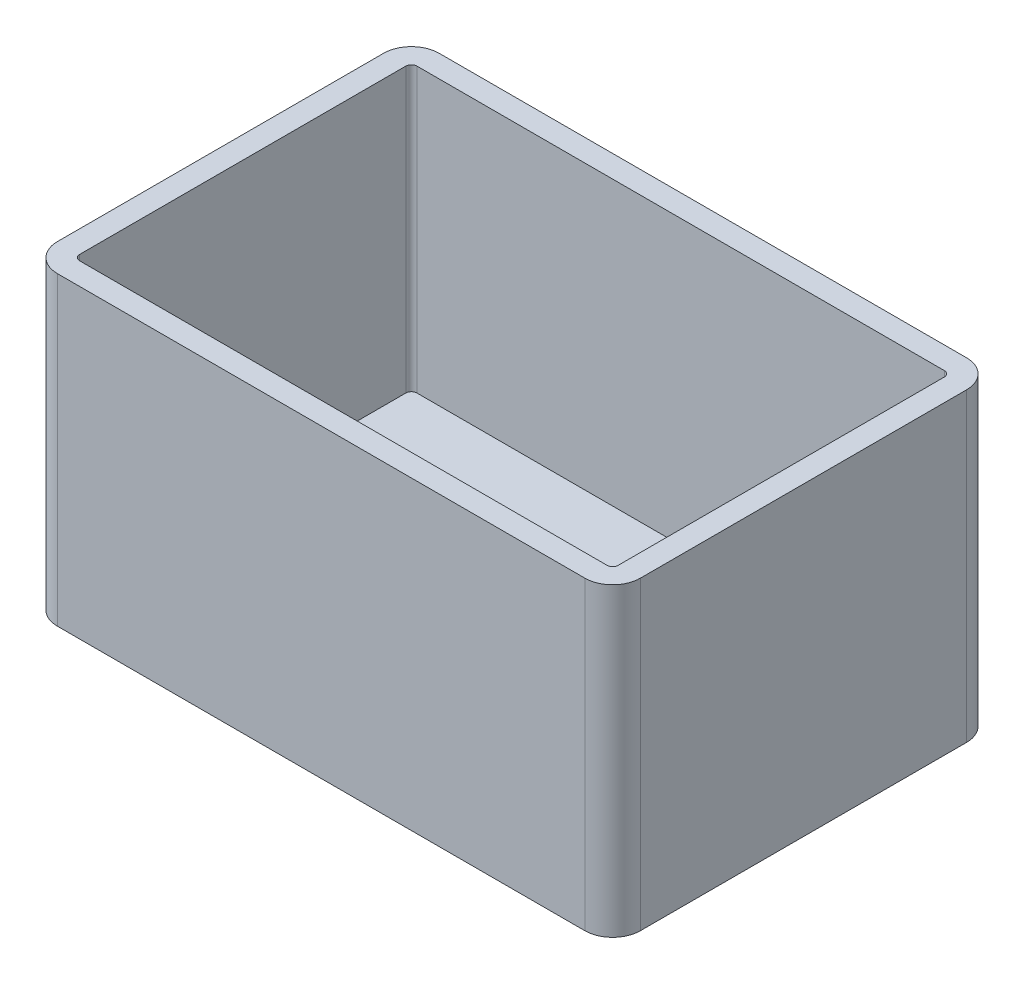
SolidWorks part; units mm, degrees
ref_plane "Front Plane" through (0, 0, 0) normal (0, 0, 1) x (1, 0, 0)
ref_plane "Top Plane" through (0, 0, 0) normal (0, 1, 0) x (1, 0, 0)
ref_plane "Right Plane" through (0, 0, 0) normal (1, 0, 0) x (0, 0, -1)
sketch "Sketch2" plane through (0, 0, 0) normal (0, 1, 0) x (1, 0, 0)
  line L1 (47.5, -34.375) -> (-47.5, -34.375)
  line L2 (52.5, -29.375) -> (52.5, 29.375)
  line L3 (47.5, 34.375) -> (-47.5, 34.375)
  line L4 (-52.5, -29.375) -> (-52.5, 29.375)
  arc A0 (-47.5, -34.375) -> (-52.5, -29.375) centre (-47.5, -29.375) cw
  arc A1 (47.5, -34.375) -> (52.5, -29.375) centre (47.5, -29.375) ccw
  arc A2 (52.5, 29.375) -> (47.5, 34.375) centre (47.5, 29.375) ccw
  arc A3 (-47.5, 34.375) -> (-52.5, 29.375) centre (-47.5, 29.375) ccw
  point P0 (0, 0)
  point P8 (-52.5, -34.375)
  point P13 (52.5, 34.375)
  point P16 (-52.5, 34.375)
  dimension "D3" = 5
  dimension "D1" = 105
  dimension "D2" = 68.75
extrude "Boss-Extrude1" add sketch "Sketch2" along normal blind 55
shell "Shell1" thickness 4 removed face at (0, 55, 0)
